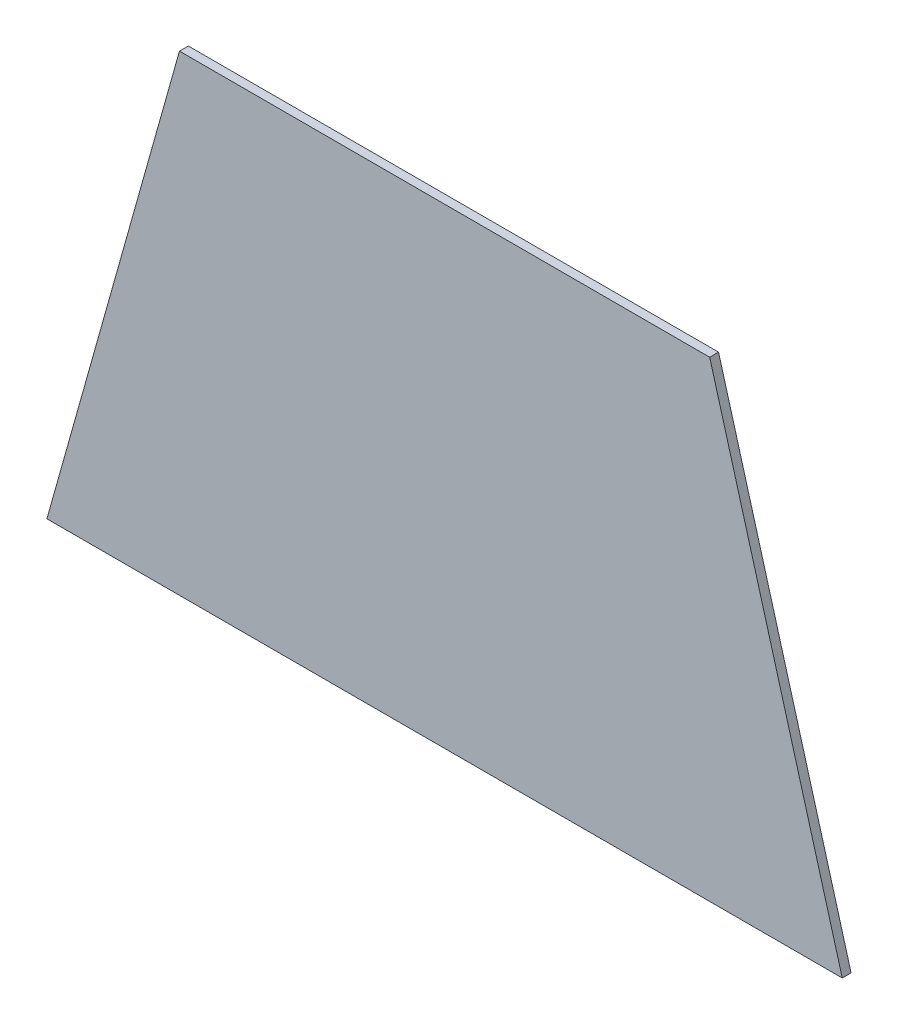
SolidWorks part; units mm, degrees
ref_plane "Front Plane" through (0, 0, 0) normal (0, 0, 1) x (1, 0, 0)
ref_plane "Top Plane" through (0, 0, 0) normal (0, 1, 0) x (1, 0, 0)
ref_plane "Right Plane" through (0, 0, 0) normal (1, 0, 0) x (0, 0, -1)
sketch "Sketch1" plane through (0, 0, 0) normal (0, 0, 1) x (1, 0, 0)
  line L0 (-135, -80) -> (135, -80)
  line L1 (135, -80) -> (90, 80)
  line L2 (90, 80) -> (-90, 80)
  line L3 (-90, 80) -> (-135, -80)
  dimension "D1" = 180
  dimension "D2" = 166.2077
  dimension "D3" = 270
  dimension "D4" = 166.2077
extrude "Boss-Extrude1" add sketch "Sketch1" along normal blind 3
